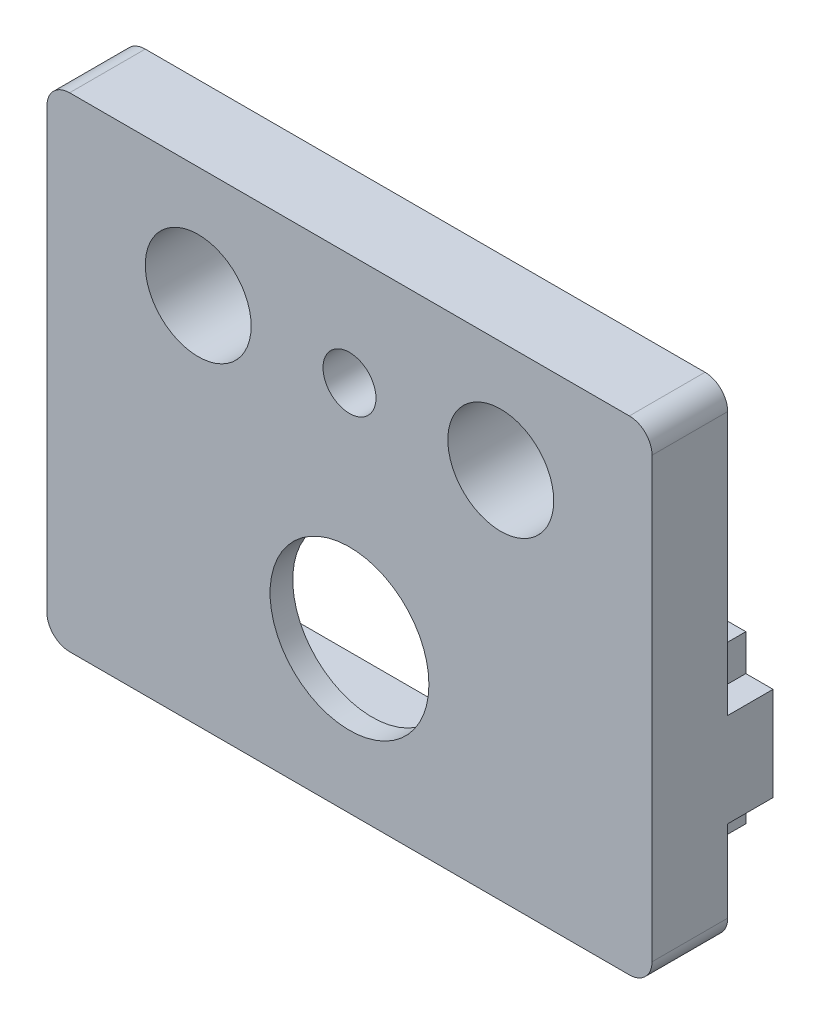
SolidWorks part; units mm, degrees
ref_plane "前视基准面" through (0, 0, 0) normal (0, 0, 1) x (1, 0, 0)
ref_plane "上视基准面" through (0, 0, 0) normal (0, 1, 0) x (1, 0, 0)
ref_plane "右视基准面" through (0, 0, 0) normal (1, 0, 0) x (0, 0, -1)
sketch "草图1" plane through (0, 0, 0) normal (0, 0, 1) x (1, 0, 0)
  line L1 (-9.5, -5.75) -> (9.5, -5.75)
  line L3 (-9.5, 5.75) -> (9.5, 5.75)
  line L5 (-20, -10) -> (20, -10)
  line L6 (-20, -10) -> (-20, 10)
  line L11 (-20, 10) -> (20, 10)
  line L12 (20, -10) -> (20, 10)
  line L13 (-20, -10) -> (20, 10) construction
  line L14 (-20, 10) -> (20, -10) construction
  arc A0 (9.5, -5.75) -> (9.5, 5.75) centre (-0.7708, 0) ccw
  arc A1 (-9.5, -5.75) -> (-9.5, 5.75) centre (0.7708, 0) cw
  point P0 (0, 0)
  point P6 (0, 0)
  point P7 (0, 0)
extrude "凸台-拉伸1" add sketch "草图1" along normal blind 3.5
sketch "草图2" plane through (0, 0, 3.5) normal (0, 0, 1) x (1, 0, 0)
  line L4 (20, -10) -> (20, 10)
  line L5 (20, 10) -> (-20, 10)
  line L6 (-20, 10) -> (-20, -10)
  line L7 (-20, -10) -> (20, -10)
  line L8 (20, -10) -> (20, 10)
  line L9 (20, 10) -> (-20, 10)
  line L10 (-20, 10) -> (-20, -10)
  line L11 (-20, -10) -> (20, -10)
  circle A0 centre (0, 0) radius 5.25
  dimension "D1" = 0
extrude "凸台-拉伸2" add sketch "草图2" along normal blind 1.5
sketch "草图3" plane through (0, 0, 5) normal (0, 0, 1) x (1, 0, 0)
  line L9 (-16.5607, 5.5) -> (-18.2, 5.5)
  line L13 (-13.9, -2.8393) -> (-13.9, 2.8393)
  line L19 (-16.5607, 5.5) -> (-13.9, 2.8393)
  line L22 (-18.2, 3.1) -> (-18.2, 5.5)
  line L23 (-18.2, 3.1) -> (-20, 3.1)
  line L24 (-18.2, -3.1) -> (-20, -3.1)
  line L25 (-18.2, -3.1) -> (-18.2, -5.5)
  line L28 (-16.5607, -5.5) -> (-13.9, -2.8393)
  line L32 (-16.5607, -5.5) -> (-18.2, -5.5)
  line L41 (18.2, 3.1) -> (20, 3.1)
  line L45 (18.2, 3.1) -> (18.2, 5.5)
  line L48 (16.5607, 5.5) -> (13.9, 2.8393)
  line L54 (13.9, -2.8393) -> (13.9, 2.8393)
  line L56 (16.5607, 5.5) -> (18.2, 5.5)
  line L63 (16.5607, -5.5) -> (18.2, -5.5)
  line L67 (16.5607, -5.5) -> (13.9, -2.8393)
  line L70 (18.2, -3.1) -> (18.2, -5.5)
  line L74 (18.2, -3.1) -> (20, -3.1)
  line L88 (-20, 3.1) -> (-20, -3.1)
  line L90 (20, 3.1) -> (20, -3.1)
  point P0 (-10, 0)
  point P8 (-10, 8.2)
  point P9 (-9.8043, 8.2)
  point P13 (-10, 8.2)
  point P14 (0, 0)
  point P20 (-5, 5)
  point P33 (-15, 5)
  point P50 (-15, -5)
  point P51 (-5, -5)
  point P52 (-10, -8.2)
  point P53 (-9.8043, -8.2)
  point P54 (10, 0)
  point P58 (10, 8.2)
  point P59 (10.1957, 8.2)
  point P63 (10, 8.2)
  point P70 (15, 5)
  point P83 (5, 5)
  point P102 (5, -5)
  point P103 (15, -5)
  point P104 (10, -8.2)
  point P105 (10.1957, -8.2)
extrude "凸台-拉伸3" add sketch "草图3" against normal blind 8
sketch "草图4" plane through (0, 0, 5) normal (0, 0, 1) x (1, 0, 0)
  line L3 (-20, 10) -> (-20, -10) construction
  line L6 (20, 10) -> (-20, 10)
  line L8 (-20, 10) -> (-20, 22)
  line L9 (-20, 22) -> (20, 22)
  line L10 (20, 22) -> (20, 10)
  circle A2 centre (-10, 14.64) radius 3.5
  circle A3 centre (10, 14.64) radius 3.5
  line M15 (20, 10) -> (-20, 10)
extrude "凸台-拉伸4" add sketch "草图4" against normal blind 5 contours L10 L9 L8 M15 region at (0, 16.2597, 5)
fillet "圆角1" radius 1.5 4 edges at (-20, 22, 2.5) (20, 22, 2.5) (20, -10, 2.5) (-20, -10, 2.5)
sketch "草图5" plane through (0, 0, 5) normal (0, 0, 1) x (1, 0, 0)
  circle A0 centre (0, 14.64) radius 1.75
extrude "切除-拉伸1" cut sketch "草图5" against normal blind 5
